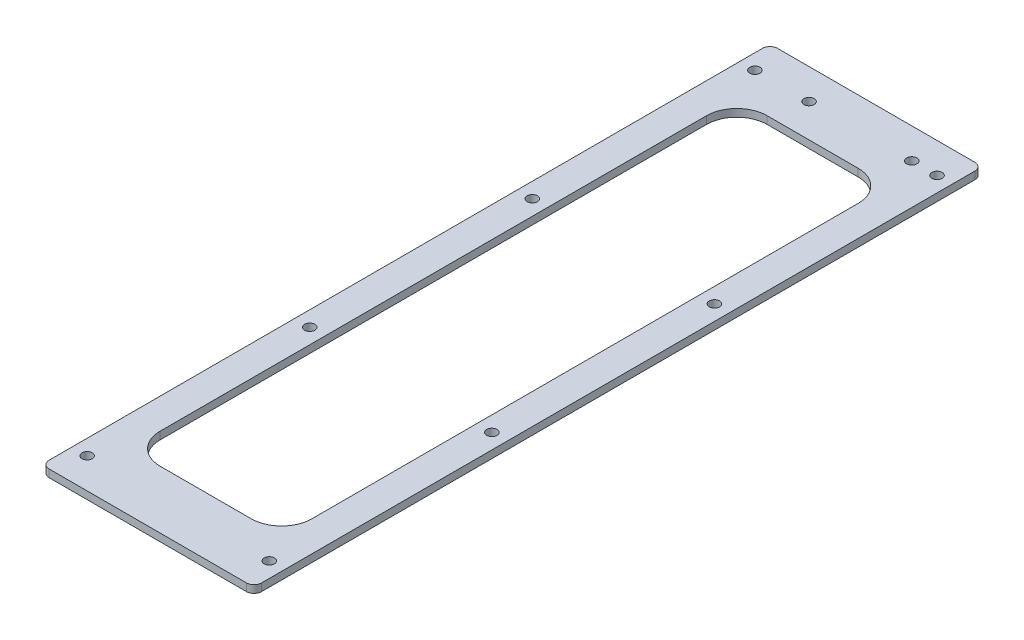
SolidWorks part; units mm, degrees
ref_plane "Front Plane" through (0, 0, 0) normal (0, 0, 1) x (1, 0, 0)
ref_plane "Top Plane" through (0, 0, 0) normal (0, 1, 0) x (1, 0, 0)
ref_plane "Right Plane" through (0, 0, 0) normal (1, 0, 0) x (0, 0, -1)
sketch "Sketch1" plane through (0, 0, 0) normal (0, 1, 0) x (1, 0, 0)
  line L1 (-44.45, 152.4) -> (44.45, 152.4)
  line L2 (-44.45, 152.4) -> (-44.45, -152.4)
  line L3 (-44.45, -152.4) -> (44.45, -152.4)
  line L4 (44.45, 152.4) -> (44.45, -152.4)
  line L14 (0, 0) -> (0, 187.5455) construction
  line L21 (0, 0) -> (44.45, 0) construction
  line L37 (-31.75, 125.8231) -> (31.75, 125.8231)
  line L40 (-31.75, 125.8231) -> (-31.75, -128.1769)
  line L43 (-31.75, -128.1769) -> (31.75, -128.1769)
  line L46 (31.75, 125.8231) -> (31.75, -128.1769)
  point P4 (0, 152.4)
  point P6 (-44.45, 0)
  dimension "D4" = 254
  dimension "D2" = 88.9
  dimension "D3" = 304.8
  dimension "D6" = 12.7
  dimension "D12" = 12.7
extrude "Boss-Extrude1" add sketch "Sketch1" along normal blind 3.175
sketch "Sketch7" plane through (0, 3.175, 0) normal (0, 1, 0) x (1, 0, 0)
  line L1 (-44.45, 152.4) -> (-44.45, -152.4) construction
  line L2 (0, 0) -> (0, 246.0772) construction
  line L3 (0, 0) -> (301.4392, 0) construction
  line L4 (44.45, 152.4) -> (-44.45, 152.4) construction
  circle A0 centre (-38.1, 139.7363) radius 2.159
  circle A10 centre (38.1, 139.7363) radius 2.159
  circle A13 centre (-38.1, 46.6029) radius 2.159
  circle A14 centre (-38.1, -46.5305) radius 2.159
  circle A15 centre (-38.1, -139.664) radius 2.159
  circle A16 centre (38.1, 46.6021) radius 2.159
  circle A17 centre (38.1, -46.5321) radius 2.159
  circle A18 centre (38.1, -139.6662) radius 2.159
  dimension "D1" = 4.318
  dimension "D3" = 6.35
  dimension "D4" = 4
  dimension "D5" = 4
  dimension "D8" = 12.6637
extrude "Cut-Extrude2" cut sketch "Sketch7" against normal through all
fillet "Fillet1" radius 12.7 4 edges at (31.75, 1.5875, 128.1769) (-31.75, 1.5875, 128.1769) (-31.75, 1.5875, -125.8231) (31.75, 1.5875, -125.8231)
sketch "Sketch8" [suppressed] plane through (0, 3.175, 0) normal (0, 1, 0) x (1, 0, 0)
  line L0 (184.15, 139.7) -> (-184.15, 139.7) construction
  line L1 (0, 139.7) -> (0, 110.7046) construction
  circle A0 centre (-15.7442, 133.35) radius 2.159
  circle A1 centre (15.7442, 133.35) radius 2.159
  dimension "D5" = 4.318
  dimension "D6" = 4.318
  dimension "D1" = 6.35
  dimension "D2" = 6.35
  dimension "D3" = 31.4884
  dimension "D4" = 15.7442
fillet "Fillet3" radius 3.175 4 edges at (-44.45, 1.5875, 152.4) (44.45, 1.5875, 152.4) (44.45, 1.5875, -152.4) (-44.45, 1.5875, -152.4)
sketch "Sketch9" plane through (0, 3.175, 0) normal (0, 1, 0) x (1, 0, 0)
  line L1 (44.45, -149.225) -> (44.45, 149.225) construction
  line L2 (41.275, 152.4) -> (-41.275, 152.4) construction
  circle A0 centre (-15.4178, 139.7) radius 2.159
  circle A1 centre (27.5844, 139.7) radius 2.159
  dimension "D1" = 4.318
  dimension "D2" = 4.318
  dimension "D5" = 12.7
  dimension "D6" = 12.7
  dimension "D3" = 59.8678
  dimension "D4" = 16.8656
extrude "Cut-Extrude4" cut sketch "Sketch9" against normal through all contours A0 | A1 region at (-15.4178, 3.175, -139.7)
